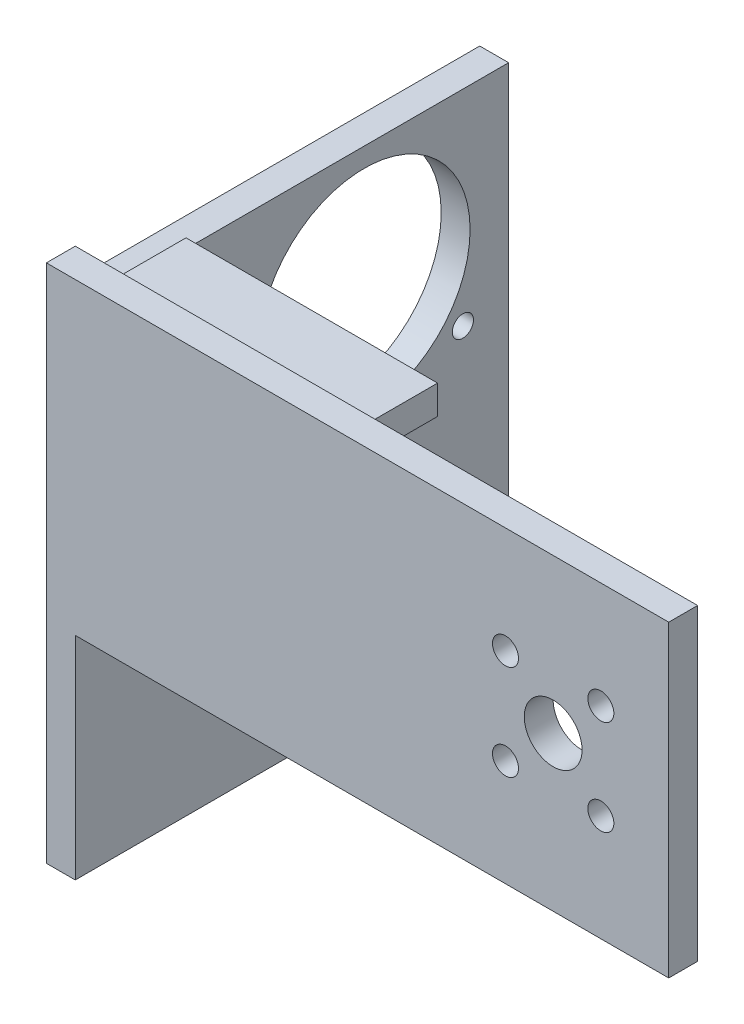
SolidWorks part; units mm, degrees
ref_plane "Front Plane" through (0, 0, 0) normal (0, 0, 1) x (1, 0, 0)
ref_plane "Top Plane" through (0, 0, 0) normal (0, 1, 0) x (1, 0, 0)
ref_plane "Right Plane" through (0, 0, 0) normal (1, 0, 0) x (0, 0, -1)
ref_plane "PZ_p27_000" through (0, 0, 27) normal (0, 0, 1) x (1, 0, 0)
sketch "S_box1" plane through (0, 0, 27) normal (0, 0, 1) x (1, 0, 0)
  line L0 (-52.625, -16) -> (12, -16)
  line L1 (12, -16) -> (12, 16)
  line L2 (12, 16) -> (-52.625, 16)
  line L3 (-52.625, 16) -> (-52.625, -16)
  dimension "P1" = 52.625
  dimension "P2" = 16
  dimension "P3" = 12
  dimension "P4" = 16
  dimension "P5" = 12
  dimension "P6" = 16
  dimension "P7" = 52.625
  dimension "P8" = 16
extrude "Boss_1" add sketch "S_box1" along normal blind 3
ref_plane "PZ_m15_000" through (0, 0, -15) normal (0, 0, 1) x (1, 0, 0)
sketch "S_box2" plane through (0, 0, -15) normal (0, 0, 1) x (1, 0, 0)
  line L0 (-52.625, -38) -> (-49.625, -38)
  line L1 (-49.625, -38) -> (-49.625, 13)
  line L2 (-49.625, 13) -> (-52.625, 13)
  line L3 (-52.625, 13) -> (-52.625, -38)
  dimension "P1" = 52.625
  dimension "P2" = 38
  dimension "P3" = 49.625
  dimension "P4" = 38
  dimension "P5" = 49.625
  dimension "P6" = 13
  dimension "P7" = 52.625
  dimension "P8" = 13
extrude "Boss_2" add sketch "S_box2" along normal blind 45
ref_plane "PZ_p18_000" through (0, 0, 18) normal (0, 0, 1) x (1, 0, 0)
sketch "S_box3" plane through (0, 0, 18) normal (0, 0, 1) x (1, 0, 0)
  line L0 (-50.125, 10.5) -> (-24, 10.5)
  line L1 (-24, 10.5) -> (-24, 13.5)
  line L2 (-24, 13.5) -> (-50.125, 13.5)
  line L3 (-50.125, 13.5) -> (-50.125, 10.5)
  dimension "P1" = 50.125
  dimension "P2" = 10.5
  dimension "P3" = 24
  dimension "P4" = 10.5
  dimension "P5" = 24
  dimension "P6" = 13.5
  dimension "P7" = 50.125
  dimension "P8" = 13.5
extrude "Boss_3" add sketch "S_box3" along normal blind 11.5
sketch "S_box4" plane through (0, 0, 18) normal (0, 0, 1) x (1, 0, 0)
  line L0 (-50.125, -16) -> (-24, -16)
  line L1 (-24, -16) -> (-24, -13)
  line L2 (-24, -13) -> (-50.125, -13)
  line L3 (-50.125, -13) -> (-50.125, -16)
  dimension "P1" = 50.125
  dimension "P2" = 16
  dimension "P3" = 24
  dimension "P4" = 16
  dimension "P5" = 24
  dimension "P6" = 13
  dimension "P7" = 50.125
  dimension "P8" = 13
extrude "Boss_4" add sketch "S_box4" along normal blind 11.5
ref_plane "PZ_p26_900" through (0, 0, 26.9) normal (0, 0, 1) x (1, 0, 0)
sketch "S_hole5" plane through (0, 0, 26.9) normal (0, 0, 1) x (1, 0, 0)
  circle A0 centre (0, 0) radius 3
  dimension "D1_S_hole5" = 6
extrude "Hole_5" cut sketch "S_hole5" along normal blind 3.2
sketch "S_hole6" plane through (0, 0, 26.9) normal (0, 0, 1) x (1, 0, 0)
  circle A0 centre (4.9497, 4.9497) radius 1.35
  dimension "D1_S_hole6" = 2.7
  dimension "P2" = 4.9497
  dimension "P3" = 4.9497
extrude "Hole_6" cut sketch "S_hole6" along normal blind 3.2
sketch "S_hole7" plane through (0, 0, 26.9) normal (0, 0, 1) x (1, 0, 0)
  circle A0 centre (-4.9497, 4.9497) radius 1.35
  dimension "D1_S_hole7" = 2.7
  dimension "P2" = 4.9497
  dimension "P3" = 4.9497
extrude "Hole_7" cut sketch "S_hole7" along normal blind 3.2
sketch "S_hole8" plane through (0, 0, 26.9) normal (0, 0, 1) x (1, 0, 0)
  circle A0 centre (-4.9497, -4.9497) radius 1.35
  dimension "D1_S_hole8" = 2.7
  dimension "P2" = 4.9497
  dimension "P3" = 4.9497
extrude "Hole_8" cut sketch "S_hole8" along normal blind 3.2
sketch "S_hole9" plane through (0, 0, 26.9) normal (0, 0, 1) x (1, 0, 0)
  circle A0 centre (4.9497, -4.9497) radius 1.35
  dimension "D1_S_hole9" = 2.7
  dimension "P2" = 4.9497
  dimension "P3" = 4.9497
extrude "Hole_9" cut sketch "S_hole9" along normal blind 3.2
ref_plane "PX_m52_725" through (-52.725, 0, 0) normal (1, 0, 0) x (0, 0, -1)
sketch "S_hole10" plane through (-52.725, 0, 0) normal (1, 0, 0) x (0, 0, -1)
  circle A0 centre (0, 0) radius 11
  dimension "D1_S_hole10" = 22
extrude "Hole_10" cut sketch "S_hole10" along normal blind 3.2
sketch "S_hole11" plane through (-52.725, 0, 0) normal (1, 0, 0) x (0, 0, -1)
  circle A0 centre (10.25, -8.3) radius 1.1
  dimension "D1_S_hole11" = 2.2
  dimension "P2" = 10.25
  dimension "P3" = 8.3
extrude "Hole_11" cut sketch "S_hole11" along normal blind 3.2
sketch "S_hole12" plane through (-52.725, 0, 0) normal (1, 0, 0) x (0, 0, -1)
  circle A0 centre (-10.25, -8.3) radius 1.1
  dimension "D1_S_hole12" = 2.2
  dimension "P2" = 10.25
  dimension "P3" = 8.3
extrude "Hole_12" cut sketch "S_hole12" along normal blind 3.2
sketch "S_hole13" plane through (-52.725, 0, 0) normal (1, 0, 0) x (0, 0, -1)
  circle A0 centre (10.25, -32.75) radius 1.1
  dimension "D1_S_hole13" = 2.2
  dimension "P2" = 10.25
  dimension "P3" = 32.75
extrude "Hole_13" cut sketch "S_hole13" along normal blind 3.2
sketch "S_hole14" plane through (-52.725, 0, 0) normal (1, 0, 0) x (0, 0, -1)
  circle A0 centre (-10.25, -32.75) radius 1.1
  dimension "D1_S_hole14" = 2.2
  dimension "P2" = 10.25
  dimension "P3" = 32.75
extrude "Hole_14" cut sketch "S_hole14" along normal blind 3.2
equation "\"plate_t\" = 3"
equation "\"clearance\" = 0.4"
